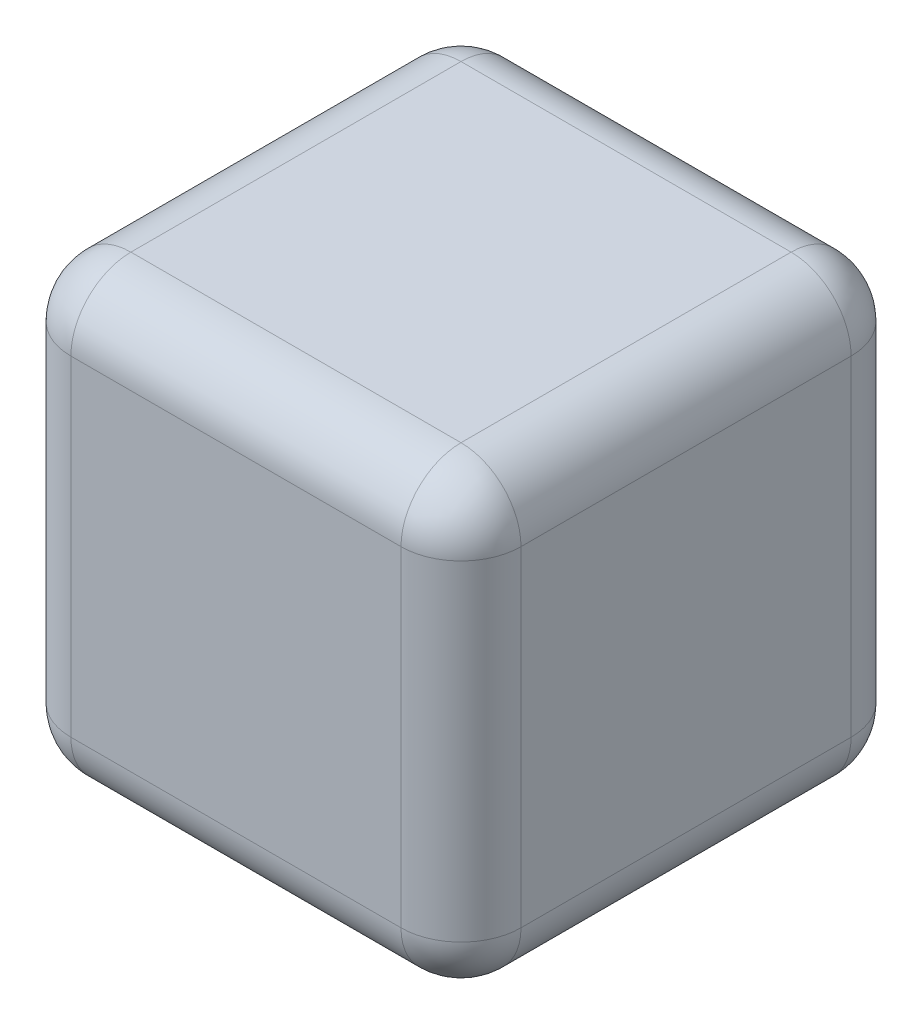
SolidWorks part; units mm, degrees
ref_plane "Front Plane" through (0, 0, 0) normal (0, 0, 1) x (1, 0, 0)
ref_plane "Top Plane" through (0, 0, 0) normal (0, 1, 0) x (1, 0, 0)
ref_plane "Right Plane" through (0, 0, 0) normal (1, 0, 0) x (0, 0, -1)
sketch "Sketch1" plane through (0, 0, 0) normal (0, 1, 0) x (1, 0, 0)
  line L0 (0, 75) -> (0, -75) construction
  line L1 (-75, 75) -> (75, 75)
  line L2 (-75, 75) -> (-75, -75)
  line L3 (-75, -75) -> (75, -75)
  line L4 (75, 75) -> (75, -75)
  line L5 (-75, 0) -> (75, 0) construction
  dimension "D1" = 150
  dimension "D2" = 150
extrude "Boss-Extrude1" add sketch "Sketch1" along normal blind 150
fillet "Fillet1" radius 20 12 edges at (0, 0, -75) (75, 75, -75) (75, 0, 0) (-75, 75, -75) (-75, 0, 0) (-75, 75, 75) (75, 75, 75) (0, 0, 75) (0, 150, -75) (75, 150, 0) (0, 150, 75) (-75, 150, 0)
shell "Shell1" thickness 1.5
